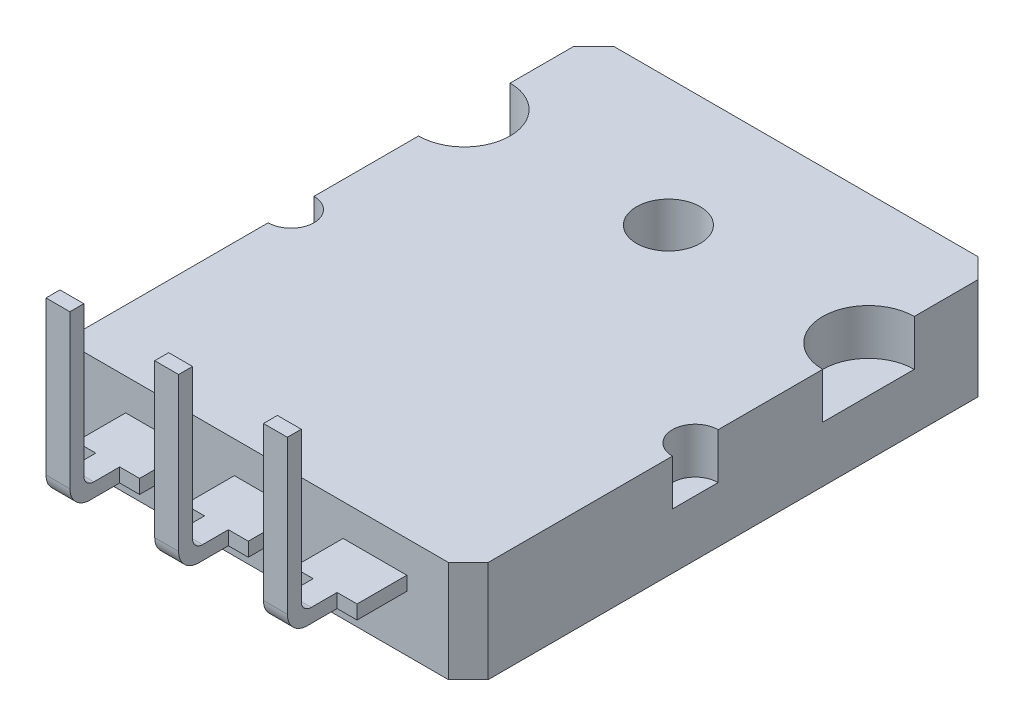
SolidWorks part; units mm, degrees
ref_plane "Спереди" through (0, 0, 0) normal (0, 0, 1) x (1, 0, 0)
ref_plane "Сверху" through (0, 0, 0) normal (0, 1, 0) x (1, 0, 0)
ref_plane "Справа" through (0, 0, 0) normal (1, 0, 0) x (0, 0, -1)
ref_plane "Плоскость1" through (0, 2.3, 0) normal (0, 1, 0) x (1, 0, 0)
sketch "Эскиз1" plane through (0, 2.3, 0) normal (0, 1, 0) x (1, 0, 0)
  line L0 (-10.15, -13.3) -> (10.15, -13.3)
  line L1 (10.15, -13.3) -> (10.15, 13.3)
  line L2 (10.15, 13.3) -> (-10.15, 13.3)
  line L3 (-10.15, 13.3) -> (-10.15, -13.3)
extrude "Бобышка-Вытянуть1" add sketch "Эскиз1" against normal blind 5.1
sketch "Эскиз2" plane through (0, 0, 13.3) normal (0, 0, 1) x (1, 0, 0)
  line L0 (3.861, 0) -> (3.861, 0.7)
  line L1 (3.861, 0.7) -> (7.061, 0.7)
  line L2 (7.061, 0.7) -> (7.061, 0)
  line L3 (7.061, 0) -> (3.861, 0)
extrude "Бобышка-Вытянуть2" add sketch "Эскиз2" along normal blind 5
sketch "Эскиз3" plane through (0, 0, 0) normal (0, -1, 0) x (1, 0, 0)
  line L0 (3.861, 15.8) -> (4.861, 15.8)
  line L1 (4.861, 15.8) -> (4.861, 18.3)
  line L2 (4.861, 18.3) -> (3.861, 18.3)
  line L3 (3.861, 18.3) -> (3.861, 15.8)
extrude "Вырез-Вытянуть1" cut sketch "Эскиз3" against normal through all
sketch "Эскиз4" plane through (0, 0, 0) normal (0, -1, 0) x (1, 0, 0)
  line L0 (6.061, 18.3) -> (6.061, 15.8)
  line L1 (6.061, 15.8) -> (7.061, 15.8)
  line L2 (7.061, 15.8) -> (7.061, 18.3)
  line L3 (7.061, 18.3) -> (6.061, 18.3)
extrude "Вырез-Вытянуть2" cut sketch "Эскиз4" against normal through all
sketch "Эскиз5" plane through (0, 0.7, 0) normal (0, 1, 0) x (-1, 0, 0)
  line L0 (-6.061, 18.3) -> (-4.861, 18.3)
  line L1 (-4.861, 18.3) -> (-4.861, 17.6)
  line L2 (-4.861, 17.6) -> (-6.061, 17.6)
  line L3 (-6.061, 17.6) -> (-6.061, 18.3)
extrude "Бобышка-Вытянуть3" add sketch "Эскиз5" along normal blind 8
sketch "Эскиз6" plane through (0, 0, 13.3) normal (0, 0, 1) x (1, 0, 0)
  line L0 (-1.6, 0) -> (-1.6, 0.7)
  line L1 (-1.6, 0.7) -> (1.6, 0.7)
  line L2 (1.6, 0.7) -> (1.6, 0)
  line L3 (1.6, 0) -> (-1.6, 0)
extrude "Бобышка-Вытянуть4" add sketch "Эскиз6" along normal blind 5
sketch "Эскиз7" plane through (0, 0, 0) normal (0, -1, 0) x (1, 0, 0)
  line L0 (-0.6, 15.8) -> (-0.6, 18.3)
  line L1 (-0.6, 18.3) -> (-1.6, 18.3)
  line L2 (-1.6, 18.3) -> (-1.6, 15.8)
  line L3 (-1.6, 15.8) -> (-0.6, 15.8)
extrude "Вырез-Вытянуть3" cut sketch "Эскиз7" against normal through all
sketch "Эскиз8" plane through (0, 0, 0) normal (0, -1, 0) x (1, 0, 0)
  line L0 (1.6, 18.3) -> (0.6, 18.3)
  line L1 (0.6, 18.3) -> (0.6, 15.8)
  line L2 (0.6, 15.8) -> (1.6, 15.8)
  line L3 (1.6, 15.8) -> (1.6, 18.3)
extrude "Вырез-Вытянуть4" cut sketch "Эскиз8" against normal through all
sketch "Эскиз9" plane through (0, 0.7, 0) normal (0, 1, 0) x (-1, 0, 0)
  line L0 (-0.6, 18.3) -> (0.6, 18.3)
  line L1 (0.6, 18.3) -> (0.6, 17.6)
  line L2 (0.6, 17.6) -> (-0.6, 17.6)
  line L3 (-0.6, 17.6) -> (-0.6, 18.3)
extrude "Бобышка-Вытянуть5" add sketch "Эскиз9" along normal blind 8
sketch "Эскиз10" plane through (0, 0, 13.3) normal (0, 0, 1) x (1, 0, 0)
  line L0 (-7.061, 0) -> (-7.061, 0.7)
  line L1 (-7.061, 0.7) -> (-3.861, 0.7)
  line L2 (-3.861, 0.7) -> (-3.861, 0)
  line L3 (-3.861, 0) -> (-7.061, 0)
extrude "Бобышка-Вытянуть6" add sketch "Эскиз10" along normal blind 5
sketch "Эскиз11" plane through (0, 0, 0) normal (0, -1, 0) x (1, 0, 0)
  line L0 (-6.061, 15.8) -> (-6.061, 18.3)
  line L1 (-6.061, 18.3) -> (-7.061, 18.3)
  line L2 (-7.061, 18.3) -> (-7.061, 15.8)
  line L3 (-7.061, 15.8) -> (-6.061, 15.8)
extrude "Вырез-Вытянуть5" cut sketch "Эскиз11" against normal through all
sketch "Эскиз12" plane through (0, 0, 0) normal (0, -1, 0) x (1, 0, 0)
  line L0 (-3.861, 18.3) -> (-4.861, 18.3)
  line L1 (-4.861, 18.3) -> (-4.861, 15.8)
  line L2 (-4.861, 15.8) -> (-3.861, 15.8)
  line L3 (-3.861, 15.8) -> (-3.861, 18.3)
extrude "Вырез-Вытянуть6" cut sketch "Эскиз12" against normal through all
sketch "Эскиз13" plane through (0, 0.7, 0) normal (0, 1, 0) x (-1, 0, 0)
  line L0 (4.861, 18.3) -> (6.061, 18.3)
  line L1 (6.061, 18.3) -> (6.061, 17.6)
  line L2 (6.061, 17.6) -> (4.861, 17.6)
  line L3 (4.861, 17.6) -> (4.861, 18.3)
extrude "Бобышка-Вытянуть7" add sketch "Эскиз13" along normal blind 8
hole_wizard "Диаметр отверстия Ø3.2 (3.2)1" positions "Эскиз15" profile "Эскиз14" hole size "Ø3.2" standard "Ansi Metric"
sketch "Эскиз15" plane through (0, 2.3, 0) normal (0, 1, 0) x (1, 0, 0)
  point P0 (0, 6.9)
sketch "Эскиз14" plane through (0, 2.3, -6.9) normal (1, 0, 0) x (0, 0, 1)
  line L0 (0, 0) -> (0, 5.1)
  line L1 (0, 5.1) -> (1.6, 5.1)
  line L2 (1.6, 5.1) -> (1.6, 0)
  line L5 (1.6, 0) -> (0, 0)
  line L11 (0, -6.35) -> (0, 107.95) construction
  dimension "Диаметр сквозного отверстия" = 3.2
  dimension "Глубина сквозного отверстия" = 5.1
hole_wizard "Диаметр отверстия Ø2.3 (2.3)1" positions "Эскиз17" profile "Эскиз16" hole size "Ø2.3" standard "Ansi Metric"
sketch "Эскиз17" plane through (0, 2.3, 0) normal (0, 1, 0) x (1, 0, 0)
  point P0 (10.15, -1.9)
  point P1 (-10.15, -1.9)
sketch "Эскиз16" plane through (10.15, 2.3, 1.9) normal (1, 0, 0) x (0, 0, 1)
  line L0 (0, 0) -> (0, 2.3)
  line L1 (0, 2.3) -> (1.15, 2.3)
  line L2 (1.15, 2.3) -> (1.15, 0)
  line L5 (1.15, 0) -> (0, 0)
  line L10 (0, 2.3) -> (-1.15, 2.3) construction
  line L11 (0, -6.35) -> (0, 107.95) construction
  dimension "Диаметр отверстия" = 2.3
  dimension "Глубина отверстия" = 2.3
  dimension "Угол заточки сверла" = 180
hole_wizard "Диаметр отверстия Ø4.6 (4.6)1" positions "Эскиз19" profile "Эскиз18" hole size "Ø4.6" standard "Ansi Metric"
sketch "Эскиз19" plane through (0, 2.3, 0) normal (0, 1, 0) x (1, 0, 0)
  point P0 (10.15, 6.8)
  point P1 (-10.15, 6.8)
sketch "Эскиз18" plane through (10.15, 2.3, -6.8) normal (1, 0, 0) x (0, 0, 1)
  line L0 (0, 0) -> (0, 2.3)
  line L1 (0, 2.3) -> (2.3, 2.3)
  line L2 (2.3, 2.3) -> (2.3, 0)
  line L5 (2.3, 0) -> (0, 0)
  line L10 (0, 2.3) -> (-2.3, 2.3) construction
  line L11 (0, -6.35) -> (0, 107.95) construction
  dimension "Диаметр отверстия" = 4.6
  dimension "Глубина отверстия" = 2.3
  dimension "Угол заточки сверла" = 180
chamfer "Фаска1" distance 1 angle 45 4 edges at (10.15, -0.25, 13.3) (-10.15, -0.25, 13.3) (10.15, -0.25, -13.3) (-10.15, -0.25, -13.3)
fillet "Скругление1" radius 0.5 3 edges at (-5.461, 0.7, 17.6) (0, 0.7, 17.6) (5.461, 0.7, 17.6) tangent propagation no
fillet "Скругление2" radius 1 3 edges at (0, 0, 18.3) (-5.461, 0, 18.3) (5.461, 0, 18.3) tangent propagation no
sketch "Эскиз20" plane through (0, -2.8, 0) normal (0, -1, 0) x (1, 0, 0)
  line L0 (9.15, -11.8858) -> (9.15, 11.8858)
  line L1 (9.15, 11.8858) -> (8.7358, 12.3)
  line L2 (8.7358, 12.3) -> (-8.7358, 12.3)
  line L3 (-8.7358, 12.3) -> (-9.15, 11.8858)
  line L4 (-9.15, 11.8858) -> (-9.15, -11.8858)
  line L5 (-9.15, -11.8858) -> (-8.7358, -12.3)
  line L6 (-8.7358, -12.3) -> (8.7358, -12.3)
  line L7 (8.7358, -12.3) -> (9.15, -11.8858)
  line L8 (10.15, -12.3) -> (10.15, 12.3)
  line L9 (10.15, 12.3) -> (9.15, 13.3)
  line L10 (9.15, 13.3) -> (-9.15, 13.3)
  line L11 (-9.15, 13.3) -> (-10.15, 12.3)
  line L12 (-10.15, 12.3) -> (-10.15, -12.3)
  line L13 (-10.15, -12.3) -> (-9.15, -13.3)
  line L14 (-9.15, -13.3) -> (9.15, -13.3)
  line L15 (9.15, -13.3) -> (10.15, -12.3)
  line L16 (10.15, -12.3) -> (10.15, 12.3)
  line L17 (10.15, 12.3) -> (9.15, 13.3)
  line L18 (9.15, 13.3) -> (-9.15, 13.3)
  line L19 (-9.15, 13.3) -> (-10.15, 12.3)
  line L20 (-10.15, 12.3) -> (-10.15, -12.3)
  line L21 (-10.15, -12.3) -> (-9.15, -13.3)
  line L22 (-9.15, -13.3) -> (9.15, -13.3)
  line L23 (9.15, -13.3) -> (10.15, -12.3)
  circle M9 centre (0, -6.9) radius 1.6
  dimension "D1" = 0
  dimension "D2" = 1
extrude "Вырез-Вытянуть7" cut sketch "Эскиз20" against normal blind 1.5 contours L6 L7 L0 L1 L2 L3 L4 L5 M9 region at (0, -2.8, 0.1256)
extrude "Бобышка-Вытянуть9" add sketch "Эскиз20<4>" against normal blind 1.5 separate body contours L6 L7 L0 L1 L2 L3 L4 L5 M9 region at (0, -2.8, 0.1256)
sketch "Эскиз20<4>" plane through (0, -2.8, 0) normal (0, -1, 0) x (1, 0, 0) same geometry as "Эскиз20"
